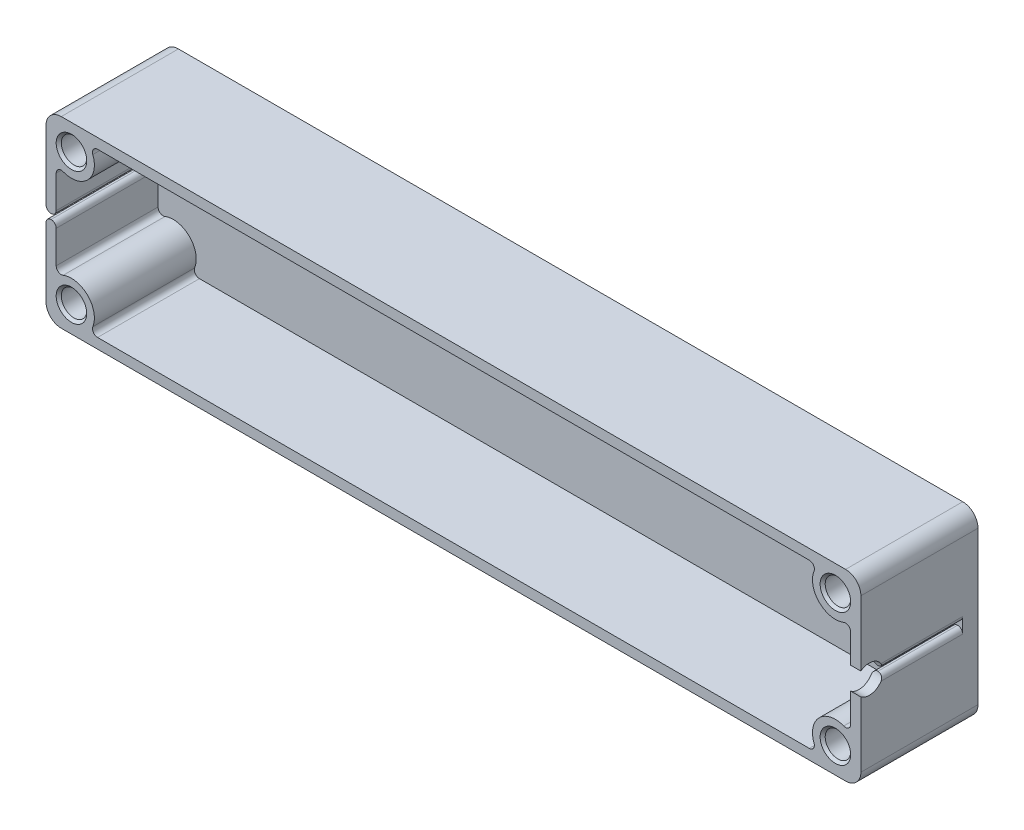
SolidWorks part; units mm, degrees
material "ABS"
ref_plane "Front" through (0, 0, 0) normal (0, 0, 1) x (1, 0, 0)
ref_plane "Top" through (0, 0, 0) normal (0, 1, 0) x (1, 0, 0)
ref_plane "Right" through (0, 0, 0) normal (1, 0, 0) x (0, 0, -1)
sketch "Sketch1" plane through (0, 0, 0) normal (0, 0, 1) x (1, 0, 0)
  line L1 (-80, 18) -> (80, 18)
  line L2 (-80, 18) -> (-80, -18)
  line L3 (-80, -18) -> (80, -18)
  line L4 (80, 18) -> (80, -18)
  point P4 (0, 18)
  point P6 (-80, 0)
  dimension "D1" = 160
  dimension "D2" = 36
extrude "Boss-Extrude1" add sketch "Sketch1" along normal blind 3
sketch "Sketch3" plane through (0, 0, 3) normal (0, 0, 1) x (1, 0, 0)
  line L0 (78, 16) -> (-78, 16)
  line L1 (-78, 16) -> (-78, -16)
  line L2 (-78, -16) -> (78, -16)
  line L3 (78, -16) -> (78, 16)
  line L4 (-80, 18) -> (-80, -18)
  line L5 (-80, -18) -> (80, -18)
  line L6 (80, -18) -> (80, 18)
  line L7 (80, 18) -> (-80, 18)
  line L8 (-80, 18) -> (-80, -18)
  line L9 (-80, -18) -> (80, -18)
  line L10 (80, -18) -> (80, 18)
  line L11 (80, 18) -> (-80, 18)
  dimension "D1" = 0
  dimension "D2" = 2
extrude "Boss-Extrude3" add sketch "Sketch3" along normal blind 20
sketch "Sketch4" plane through (0, 0, 23) normal (0, 0, 1) x (1, 0, 0)
  line L0 (78, -16) -> (78, 16) construction
  line L1 (78, 0.5) -> (80, 0.5)
  line L2 (78, 0.5) -> (78, -0.5)
  line L3 (78, -0.5) -> (80, -0.5)
  line L4 (80, 0.5) -> (80, -0.5)
  line L5 (80, -18) -> (80, 18) construction
  point P8 (78, 0)
  dimension "D1" = 1
extrude "Cut-Extrude1" cut sketch "Sketch4" against normal up to surface (20 mm away) up to face at (0, 0, 3)
sketch "Sketch5" plane through (0, 0, 3) normal (0, 0, 1) x (1, 0, 0)
  line L0 (80, 0.5) -> (80, 18) construction
  line L1 (80, 18) -> (-80, 18) construction
  line L2 (-80, -18) -> (80, -18) construction
  circle A2 centre (75, 13) radius 4.5
  circle A3 centre (75, -13) radius 4.5
  dimension "D4" = 9
  dimension "D1" = 5
  dimension "D2" = 5
  dimension "D3" = 5
extrude "Boss-Extrude4" add sketch "Sketch5" along normal up to surface (20 mm away) up to face at (26.3333, 0, 23)
hole_wizard "Ø5.0mm Dowel Hole1" positions "Sketch6" profile "Sketch7" hole size "Ø5.0" standard "ANSI Metric"
sketch "Sketch6" plane through (0, 0, 23) normal (0, 0, 1) x (1, 0, 0)
  point P0 (75, 13)
  point P3 (75, -13)
sketch "Sketch7" plane through (75, 13, 23) normal (1, 0, 0) x (0, -1, 0)
  line L0 (0, 0) -> (0, 4.6)
  line L1 (0, 4.6) -> (2.5, 4.6)
  line L2 (2.5, 4.6) -> (2.5, 0.5)
  line L3 (2.5, 0.5) -> (3, 0)
  line L5 (3, 0) -> (0, 0)
  line L6 (-2.5, 0.5) -> (-3, 0) construction
  line L10 (0, 4.6) -> (-2.5, 4.6) construction
  line L11 (0, -6.35) -> (0, 107.95) construction
  dimension "Hole Dia." = 5
  dimension "Hole Depth" = 4.6
  dimension "Near C'Sink Dia." = 6
  dimension "Near C'Sink Angle" = 90
  dimension "Drill Angle" = 180
fillet "Fillet3" radius 3 4 edges at (-80, 18, 11.5) (80, 18, 11.5) (-80, -18, 11.5) (80, -18, 11.5)
hole_wizard "M5 Clearance Hole2" positions "Sketch11" profile "Sketch12" hole size "M5" standard "ANSI Metric" end condition through all
sketch "Sketch11" plane through (0, 0, 0) normal (0, 0, -1) x (-1, 0, 0)
  line L0 (-80, -15) -> (-80, 15) construction
  line L1 (80, 15) -> (80, -15) construction
  point P0 (-70, 0)
  point P2 (70, 0)
  dimension "D1" = 10
  dimension "D2" = 10
sketch "Sketch12" plane through (70, 0, 0) normal (1, 0, 0) x (0, 1, 0)
  line L0 (0, 0) -> (0, 23)
  line L1 (0, 23) -> (2.75, 23)
  line L2 (2.75, 23) -> (2.75, 0)
  line L5 (2.75, 0) -> (0, 0)
  line L11 (0, -6.35) -> (0, 107.95) construction
  dimension "Thru Hole Dia." = 5.5
  dimension "Thru Hole Depth" = 23
mirror "Mirror2" about plane through (0, 0, 0) normal (1, 0, 0) of "Boss-Extrude4", "Ø5.0mm Dowel Hole1", "M5 Clearance Hole2", "Cut-Extrude1"
fillet "Fillet4" radius 1 16 edges at (-78, -9.6459, 13) (-78, -0.5, 13) (-80, -0.5, 13) (-80, 0.5, 13) (-78, 0.5, 13) (-78, 9.6459, 13) (-71.6459, 16, 13) (71.6459, 16, 13) (78, 0.5, 13) (80, 0.5, 13) (80, -0.5, 13) (78, -0.5, 13) (78, -9.6459, 13) (71.6459, -16, 13) (-71.6459, -16, 13) (78, 9.6459, 13)
hole_wizard "M5 Clearance Hole3" positions "Sketch13" profile "Sketch14" hole size "M5" standard "ANSI Metric"
sketch "Sketch13" plane through (80, 0, 0) normal (1, 0, 0) x (0, 0, -1)
  point P0 (-21.3514, 0)
sketch "Sketch14" plane through (80, 0, 21.3514) normal (0, 1, 0) x (0, 0, -1)
  line L0 (0, 0) -> (0, 11.6524)
  line L1 (0, 11.6524) -> (2.75, 10)
  line L2 (2.75, 10) -> (2.75, 0)
  line L5 (2.75, 0) -> (0, 0)
  line L10 (0, 11.6524) -> (-2.75, 10) construction
  line L11 (0, -6.35) -> (0, 107.95) construction
  dimension "Hole Dia." = 5.5
  dimension "Hole Depth" = 10
  dimension "Drill Angle" = 118
